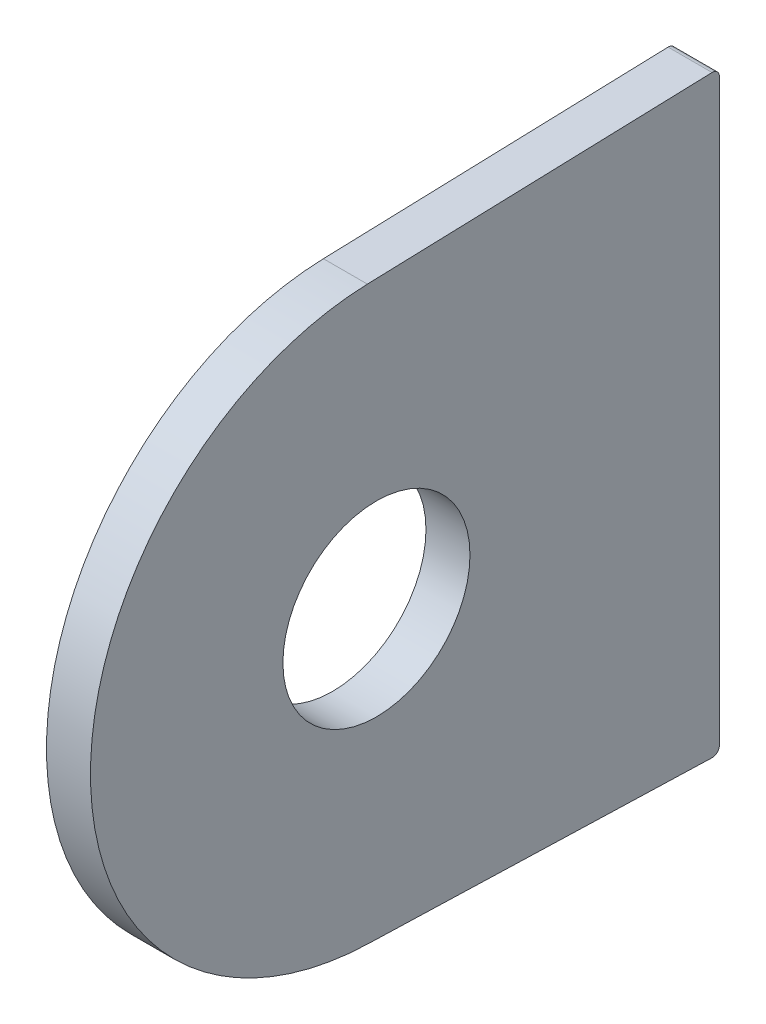
SolidWorks part; units mm, degrees
material "ASTM A36 Steel"
ref_plane "X-Y Datum" through (0, 0, 0) normal (0, 0, 1) x (1, 0, 0)
ref_plane "X-Z Datum" through (0, 0, 0) normal (0, 1, 0) x (1, 0, 0)
ref_plane "Y-Z Datum" through (0, 0, 0) normal (1, 0, 0) x (0, 0, -1)
sketch "Sketch1" plane through (0, 0, 0) normal (1, 0, 0) x (0, 0, -1)
  line L0 (24.747, -21.4312) -> (-0.653, -20.6272)
  line L1 (24.747, 21.4312) -> (-0.653, 20.6272)
  line L2 (24.747, -21.4312) -> (24.747, 21.4312)
  line L3 (6.75, 0) -> (24.747, 0) construction
  arc A0 (-0.653, 20.6272) -> (-0.653, -20.6272) centre (0, 0) ccw
  circle A1 centre (0, 0) radius 6.75
  dimension "D1" = 41.275
  dimension "D2" = 13.5
  dimension "D3" = 42.8625
  dimension "D5" = 13.8875
  dimension "D4" = 25.4
extrude "Boss-Extrude1" add sketch "Sketch1" along normal mid plane 3.175 contours A1 | L0 L2 L1 A0 A1 region at (0, -20.4053, -12.0668) region at (0, 0, 0)
fillet "Fillet1" radius 0.508 1 edges at (0, -21.4313, -24.747)
fillet "Fillet2" radius 0.508 1 edges at (0, 21.4313, -24.747)
hole_wizard "M12 Clearance Hole1" positions "Sketch4" profile "Sketch5" hole size "M12" standard "ANSI Metric" end condition through all
sketch "Sketch4" plane through (-1.5875, 0, 0) normal (-1, 0, 0) x (0, 0, 1)
  point P0 (0, 0)
sketch "Sketch5" plane through (-1.5875, 0, 0) normal (0, 1, 0) x (0, 0, 1)
  line L0 (0, 0) -> (0, 3.175)
  line L1 (0, 3.175) -> (6.75, 3.175)
  line L2 (6.75, 3.175) -> (6.75, 0)
  line L5 (6.75, 0) -> (0, 0)
  line L11 (0, -6.35) -> (0, 107.95) construction
  dimension "Thru Hole Dia." = 13.5
  dimension "Thru Hole Depth" = 3.175
